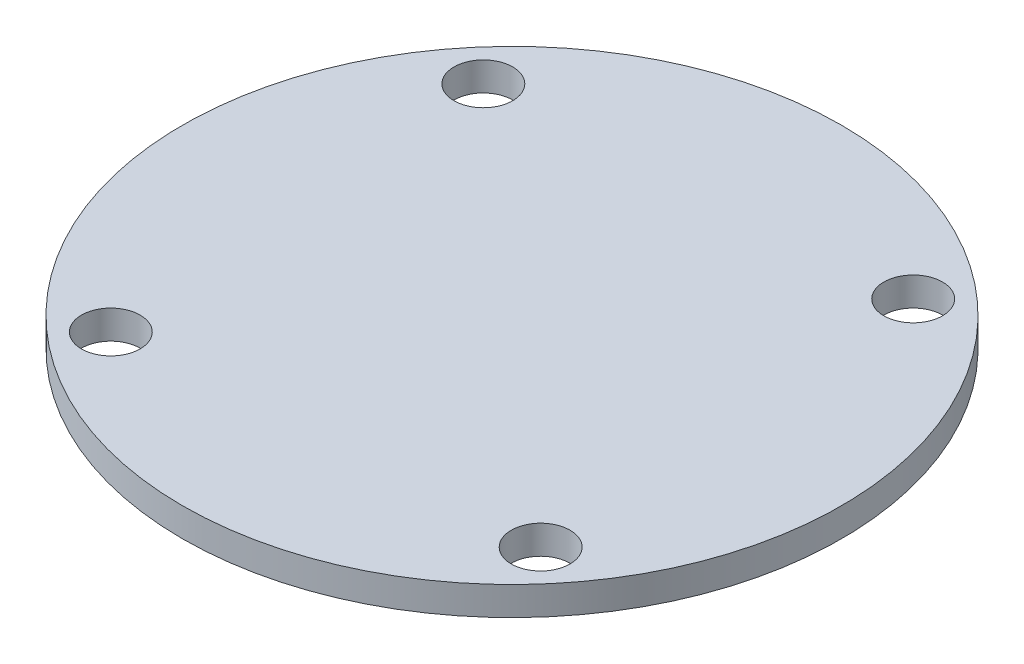
SolidWorks part; units mm, degrees
ref_plane "Front Plane" through (0, 0, 0) normal (0, 0, 1) x (1, 0, 0)
ref_plane "Top Plane" through (0, 0, 0) normal (0, 1, 0) x (1, 0, 0)
ref_plane "Right Plane" through (0, 0, 0) normal (1, 0, 0) x (0, 0, -1)
sketch "Sketch1" plane through (0, 0, 0) normal (0, 1, 0) x (1, 0, 0)
  circle A0 centre (0, 0) radius 29.21
  dimension "D1" = 58.42
extrude "Boss-Extrude1" add sketch "Sketch1" along normal blind 2.54
sketch "Sketch2" plane through (0, 2.54, 0) normal (0, 1, 0) x (1, 0, 0)
  circle A0 centre (0, 0) radius 29.21 construction
  circle A1 centre (-16.51, -19.05) radius 2.6
  point P0 (-16.51, -19.05)
  dimension "D2" = 5.2
  dimension "D1" = 19.05
  dimension "D3" = 16.51
extrude "Cut-Extrude1" cut sketch "Sketch2" against normal through all
pattern_circular "CirPattern1" count 4 over 360 about axis through (0, 2.54, 0) along (0, 1, 0) of "Cut-Extrude1"
